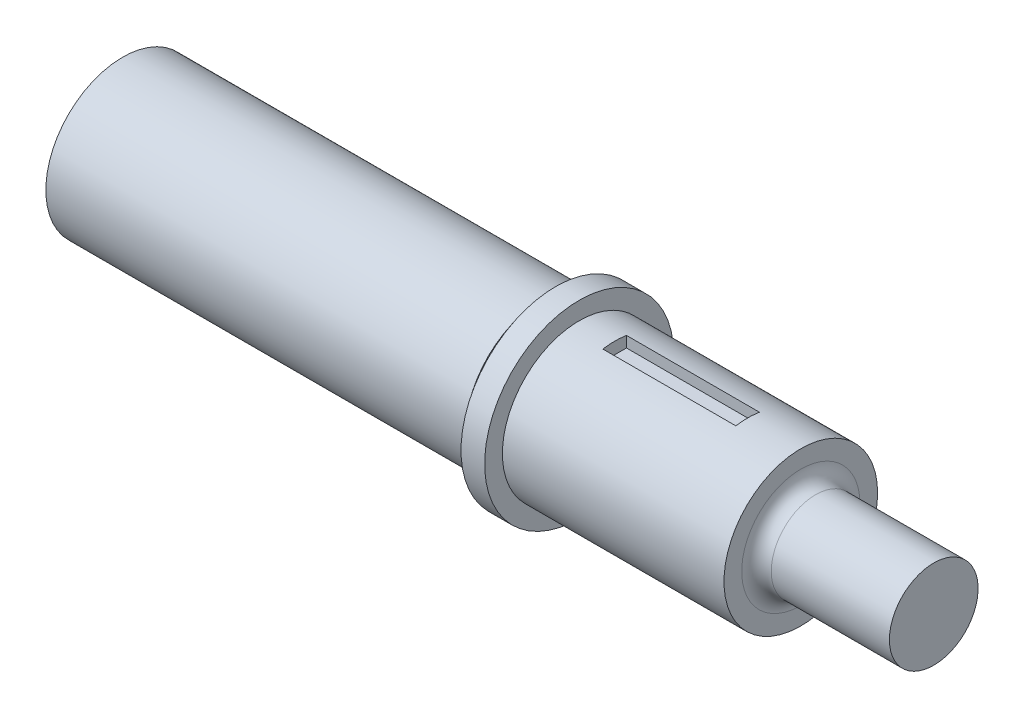
SolidWorks part; units mm, degrees
ref_plane "Front Plane" through (0, 0, 0) normal (0, 0, 1) x (1, 0, 0)
ref_plane "Top Plane" through (0, 0, 0) normal (0, 1, 0) x (1, 0, 0)
ref_plane "Right Plane" through (0, 0, 0) normal (1, 0, 0) x (0, 0, -1)
sketch "Sketch1" plane through (0, 0, 0) normal (1, 0, 0) x (0, 0, -1)
  circle A0 centre (0, 0) radius 26
extrude "Boss-Extrude1" add sketch "Sketch1" along normal blind 142
sketch "Sketch2" plane through (142, 0, 0) normal (1, 0, 0) x (0, 0, -1)
  circle A0 centre (0, 0) radius 22
extrude "Boss-Extrude2" add sketch "Sketch2" along normal blind 4.5
sketch "Sketch3" plane through (146.5, 0, 0) normal (1, 0, 0) x (0, 0, -1)
  circle A0 centre (0, 0) radius 32
extrude "Boss-Extrude3" add sketch "Sketch3" along normal blind 8
sketch "Sketch4" plane through (154.5, 0, 0) normal (1, 0, 0) x (0, 0, -1)
  circle A0 centre (0, 0) radius 26
extrude "Boss-Extrude4" add sketch "Sketch4" along normal blind 75
hole_wizard "Ø12.0 (12) Diameter Hole1" positions "3DSketch1" profile "Sketch5" hole size "Ø12.0" standard "ISO"
sketch3d "3DSketch1"
  line L0 (142, 0, 0) -> (0, 0, 0) construction
  point P0 (0, 0, 0)
  point P3 (0, 0, 0)
  point P6 (0, 0, 0)
  point P8 (0, 0, 0)
  point P12 (-153.5637, 12.3509, 0)
  point P14 (0, 0, 0)
  point P16 (0, 0, 0)
  point P18 (0, 0, 0)
  dimension "D1" = 0
sketch "Sketch5" plane through (0, 0, 0) normal (0, 1, 0) x (0, 0, 1)
  line L0 (0, 0) -> (0, 26.6052)
  line L1 (0, 26.6052) -> (6, 23)
  line L2 (6, 23) -> (6, 0)
  line L5 (6, 0) -> (0, 0)
  line L10 (0, 26.6052) -> (-6, 23) construction
  line L11 (0, -6.35) -> (0, 107.95) construction
  dimension "Hole Dia." = 12
  dimension "Hole Depth" = 23
  dimension "Drill Angle" = 118
sketch "Sketch6" plane through (229.5, 0, 0) normal (1, 0, 0) x (0, 0, -1)
  circle A0 centre (0, 0) radius 15
extrude "Boss-Extrude5" add sketch "Sketch6" along normal blind 45
fillet "Fillet2" radius 5 1 edges at (229.5, 0, -15)
sketch "Sketch7" plane through (0, 0, 0) normal (0, 1, 0) x (1, 0, 0)
  line L0 (229.5, 26) -> (154.5, 26) construction
  line L1 (166.5, -4) -> (211.5, -4)
  line L2 (166.5, -4) -> (166.5, 4)
  line L3 (166.5, 4) -> (211.5, 4)
  line L4 (211.5, -4) -> (211.5, 4)
  line L5 (154.5, -26) -> (229.5, -26) construction
  line L7 (154.5, -32) -> (154.5, 32) construction
  dimension "D1" = 30
  dimension "D2" = 30
  dimension "D4" = 12
  dimension "D3" = 45
extrude "Cut-Extrude1" cut sketch "Sketch7" against normal blind 4 from offset 26
sketch "Esquisse1" plane through (0, 0, 0) normal (-1, 0, 0) x (0, 0, 1)
  line L0 (0, -6) -> (0, -26) construction
  circle A0 centre (0, 0) radius 26 construction
  circle A4 centre (0, 0) radius 6 construction
  circle A5 centre (0, 0) radius 6 construction
  point P14 (0, -16)
  dimension "D1" = 20
  dimension "D2" = 0
hole_wizard "M8 Clearance Hole1" positions "Esquisse1" profile "Esquisse3" hole size "M8" standard "ANSI Metric"
sketch "Esquisse3" plane through (0, -16, 0) normal (0, 1, 0) x (0, 0, 1)
  line L0 (0, 0) -> (0, 15.5236)
  line L1 (0, 15.5236) -> (4.2, 13)
  line L2 (4.2, 13) -> (4.2, 0)
  line L5 (4.2, 0) -> (0, 0)
  line L10 (0, 15.5236) -> (-4.2, 13) construction
  line L11 (0, -6.35) -> (0, 107.95) construction
  dimension "Diamètre du perçage" = 8.4
  dimension "Profondeur du perçage" = 13
  dimension "Angle de pointe" = 118
equation "\"D2@Sketch7\"=\"D1@Sketch7\""
